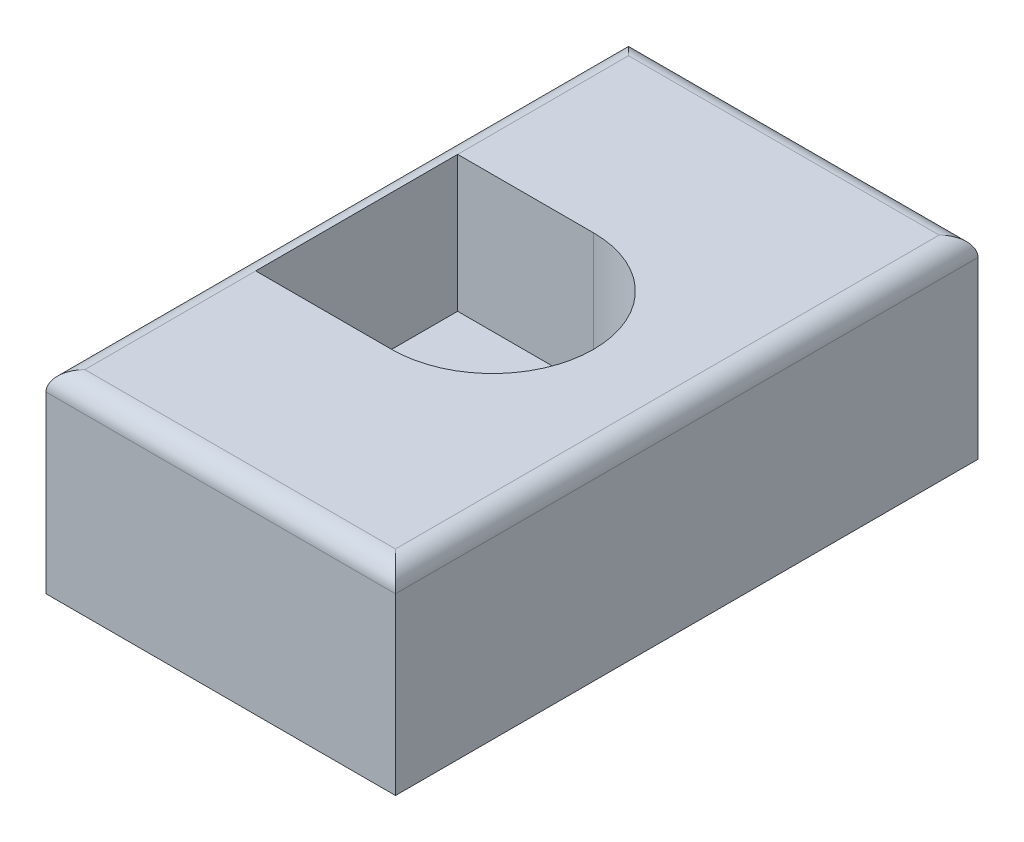
SolidWorks part; units mm, degrees
ref_plane "Front Plane" through (0, 0, 0) normal (0, 0, 1) x (1, 0, 0)
ref_plane "Top Plane" through (0, 0, 0) normal (0, 1, 0) x (1, 0, 0)
ref_plane "Right Plane" through (0, 0, 0) normal (1, 0, 0) x (0, 0, -1)
sketch "Sketch2" plane through (0, 15, 0) normal (0, 1, 0) x (1, 0, 0)
  line L0 (0, -35.7819) -> (0, 677.0007) construction
  line L8 (-10, 298.8635) -> (10, 298.8635)
  line L9 (-10, 298.8635) -> (-10, 328.8635)
  line L10 (-10, 328.8635) -> (10, 328.8635)
  line L11 (10, 298.8635) -> (10, 328.8635)
  line L12 (-10, 298.8635) -> (10, 328.8635) construction
  line L13 (-10, 328.8635) -> (10, 298.8635) construction
  dimension "D1" = 20
  dimension "D2" = 30
extrude "Extrude1" add sketch "Sketch2" along normal blind 10
sketch "Sketch3" plane through (0, 25, 0) normal (0, 1, 0) x (1, 0, 0)
  line L0 (-10, 313.8635) -> (10, 313.8635) construction
  line L1 (-10, 328.8635) -> (-10, 298.8635) construction
  line L2 (10, 298.8635) -> (10, 328.8635) construction
  line L3 (0, 328.8635) -> (0, 298.8635) construction
  line L4 (10, 328.8635) -> (-10, 328.8635) construction
  line L5 (-10, 298.8635) -> (10, 298.8635) construction
  line L6 (0, 319.0635) -> (-7, 319.0635)
  line L7 (0, 308.6635) -> (-7, 308.6635)
  line L8 (-10, 333.2737) -> (-10, 294.5222) construction
  line L9 (-7, 319.0635) -> (-7, 308.6635)
  line L11 (-7, 333.2737) -> (-7, 294.5222) construction
  arc A0 (0, 308.6635) -> (0, 319.0635) centre (0, 313.8635) ccw
  dimension "D1" = 10.4
  dimension "D2" = 3
extrude "Cut-Extrude1" cut sketch "Sketch3" against normal blind 7
sketch "Sketch4" plane through (0, 18, 0) normal (0, 1, 0) x (1, 0, 0)
  circle A0 centre (0, 313.8635) radius 2.65
  dimension "D1" = 5.3
extrude "Cut-Extrude2" cut sketch "Sketch4" against normal blind 17
sketch "Sketch7" plane through (0, 0, -298.8635) normal (0, 0, 1) x (1, 0, 0)
  line L0 (-10, 15) -> (10, 15) construction
  line L1 (-10, 25) -> (-8, 25)
  line L2 (-10, 25) -> (-10, 15)
  line L3 (-10, 15) -> (-8, 15)
  line L4 (-8, 25) -> (-8, 15)
  dimension "D1" = 2
extrude "Extrude2" cut sketch "Sketch7" against normal blind 30
fillet "Fillet1" radius 1 4 edges at (1, 25, -298.8635) (10, 25, -313.8635) (-8, 25, -313.8635) (1, 25, -328.8635)
